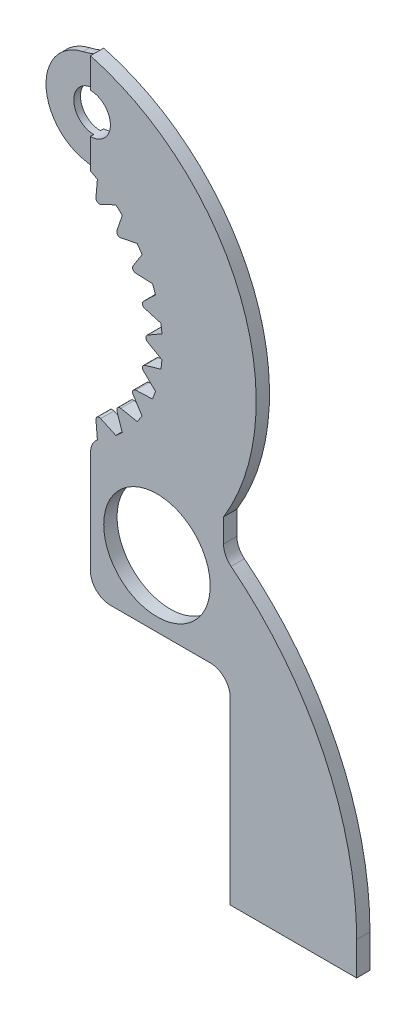
SolidWorks part; units mm, degrees
ref_plane "Front Plane" through (0, 0, 0) normal (0, 0, 1) x (1, 0, 0)
ref_plane "Top Plane" through (0, 0, 0) normal (0, 1, 0) x (1, 0, 0)
ref_plane "Right Plane" through (0, 0, 0) normal (1, 0, 0) x (0, 0, -1)
sketch "Sketch1" plane through (0, 0, 0) normal (0, 0, 1) x (1, 0, 0)
  line L0 (0, 50) -> (0, -50) construction
  line L1 (-20, 50) -> (20, 50) construction
  line L2 (-20, 50) -> (-20, -50) construction
  line L3 (-20, -50) -> (20, -50) construction
  line L4 (20, 50) -> (20, -50) construction
  line L5 (-20, 50) -> (20, -50) construction
  line L6 (-20, -50) -> (20, 50) construction
  line L7 (-20, -20) -> (20, -20) construction
  line L8 (-20, -5) -> (20, -5) construction
  line L9 (-20, -5) -> (-20, -20)
  line L10 (-20, -20) -> (0, -20)
  line L11 (20, -50) -> (1, -50)
  line L12 (1, -50) -> (1, -20)
  line L13 (20, -50) -> (20, -5)
  line L14 (20, -5) -> (0, -5)
  line L15 (-20, 0) -> (0, 0) construction
  line L16 (-20, -5) -> (-20, 0)
  line L17 (0, -5) -> (0, 0)
  line L18 (-20, 50) -> (-20, 35)
  line L19 (1, -20) -> (0, -20)
  arc A0 (-20, 50) -> (0, 0) centre (-28.75, 17.5) cw
  arc A1 (-20, 35) -> (-20, 0) centre (-28.75, 17.5) cw
  point P0 (0, 0)
  point P8 (1, -50)
  point P18 (-20, 35)
  dimension "D1" = 40
  dimension "D2" = 100
  dimension "D4" = 30
  dimension "D5" = 15
  dimension "D6" = 5
  dimension "D7" = 15
  dimension "D8" = 19
extrude "Boss-Extrude1" add sketch "Sketch1" along normal blind 2
sketch "Sketch2" plane through (0, 0, 2) normal (0, 0, 1) x (1, 0, 0)
  line L0 (-20, 35) -> (-20, 0) construction
  line L1 (-20, 17.5) -> (-9.1844, 17.5) construction
  line L3 (-12.1844, 17.5) -> (-8.5113, 19.6207)
  line L4 (-12.1844, 17.5) -> (-8.5113, 15.3793)
  line L5 (-8.5113, 19.6207) -> (-8.5113, 15.3793)
  arc A0 (-20, 0) -> (-20, 35) centre (-28.75, 17.5) ccw construction
extrude "Boss-Extrude2" add sketch "Sketch2" against normal up to vertex (2 mm away) up to point (-20, 35, 0)
pattern_circular "CirPattern1" count 5 every 13.75 about axis through (-28.75, 17.5, 2) along (0, 0, -1) of "Boss-Extrude2"
pattern_circular "CirPattern2" count 5 every 13.75 about axis through (-28.75, 17.5, 2) along (0, 0, -1) of "CirPattern1" reverse direction yes
sketch "Sketch3" plane through (0, 0, 0) normal (0, 0, -1) x (-1, 0, 0)
  line L1 (0, 0) -> (20, 0) construction
  line L2 (0, 0) -> (0, -20) construction
  line L3 (0, -20) -> (20, -20) construction
  line L4 (20, 0) -> (20, -20) construction
  circle A0 centre (10, -10) radius 8
  dimension "D1" = 16
extrude "Cut-Extrude1" cut sketch "Sketch3" against normal through all
ref_plane "Plane1" through (0, 0, 1) normal (0, 0, 1) x (1, 0, 0)
sketch "Sketch4" plane through (0, 0, 1) normal (0, 0, 1) x (1, 0, 0)
  line L0 (-20, 50) -> (-20, 35) construction
  circle A0 centre (-20, 42.5) radius 7.1703
extrude "Boss-Extrude3" add sketch "Sketch4" along normal blind 0.5 and the other way blind 0.5
sketch "Sketch5" plane through (0, 0, 1) normal (0, 0, 1) x (1, 0, 0)
  line L0 (-20, 49.6703) -> (-20, 35.3297) construction
  circle A0 centre (-20, 42.5) radius 3
  dimension "D1" = 6
extrude "Cut-Extrude2" cut sketch "Sketch5" against normal through all and the other way through all
fillet "Fillet1" radius 50 1 edges at (20, -5, 1)
fillet "Fillet2" radius 10 1 edges at (-20, 49.6703, 1)
fillet "Fillet3" radius 3 5 edges at (0, -5, 1) (1, -20, 1) (-20, -20, 1) (-20, 0, 1) (-20, 35.3297, 1)
fillet "Fillet4" radius 0.5 9 edges at (-19.2484, 3.9303, 1) (-16.2953, 6.5775, 1) (-14.0561, 9.8509, 1) (-12.6591, 13.5626, 1) (-12.1844, 17.5, 1) (-12.6591, 21.4374, 1) (-14.0561, 25.1491, 1) (-16.2953, 28.4225, 1) (-19.2484, 31.0697, 1)
